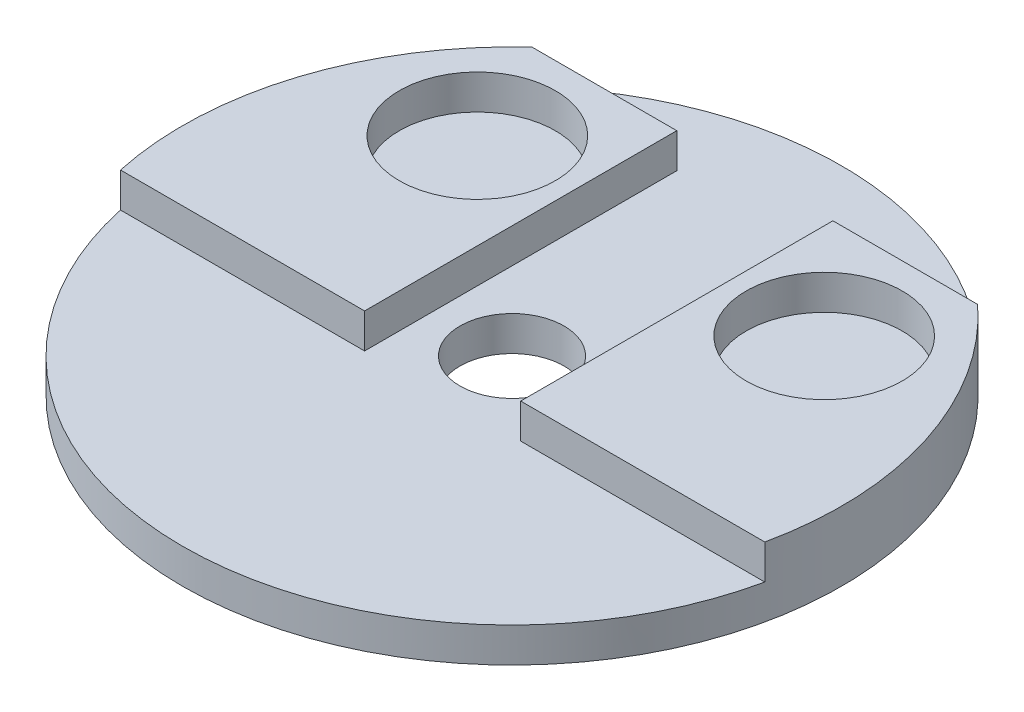
SolidWorks part; units mm, degrees
ref_plane "前视基准面" through (0, 0, 0) normal (0, 0, 1) x (1, 0, 0)
ref_plane "上视基准面" through (0, 0, 0) normal (0, 1, 0) x (1, 0, 0)
ref_plane "右视基准面" through (0, 0, 0) normal (1, 0, 0) x (0, 0, -1)
sketch "草图1" plane through (0, 0, 0) normal (0, 1, 0) x (1, 0, 0)
  line L0 (4.6435, -1) -> (-4.6435, -1)
  line L1 (-3.2113, 3.5) -> (3.2113, 3.5)
  line L2 (0, 0) -> (1.9515, 0) construction
  line L3 (0, 0) -> (-3.2113, 0) construction
  line L4 (0, 0) -> (0, 4.75) construction
  line L5 (0, 0) -> (0, -2.7629) construction
  line L7 (-1.125, 3.5) -> (1.125, 3.5)
  line L8 (-1.125, 3.5) -> (-1.125, -1)
  line L9 (-1.125, -1) -> (1.125, -1)
  line L10 (1.125, 3.5) -> (1.125, -1)
  circle A0 centre (0, 0) radius 0.75
  circle A1 centre (0, 0) radius 4.75
  circle A2 centre (-2.5, 2) radius 1.125
  circle A3 centre (2.5, 2) radius 1.125
  dimension "D1" = 1.5
  dimension "D2" = 9.5
  dimension "D5" = 2.25
  dimension "D3" = 1
  dimension "D4" = 3.5
  dimension "D6" = 2.5
  dimension "D7" = 2
  dimension "D8" = 2.25
extrude "凸台-拉伸1" add sketch "草图1" against normal blind 0.5 contours A0 | A1 region at (0, 0, 0)
extrude "凸台-拉伸2" add sketch "草图1<3>" along normal blind 0.5 contours L0 A1 L1 L10 A3 | L1 A1 L0 L8 A2 region at (2.8818, 0, -0.7571) region at (-2.8818, 0, -0.7571)
sketch "草图1<3>" plane through (0, 0, 0) normal (0, 1, 0) x (1, 0, 0) same geometry as "草图1"
